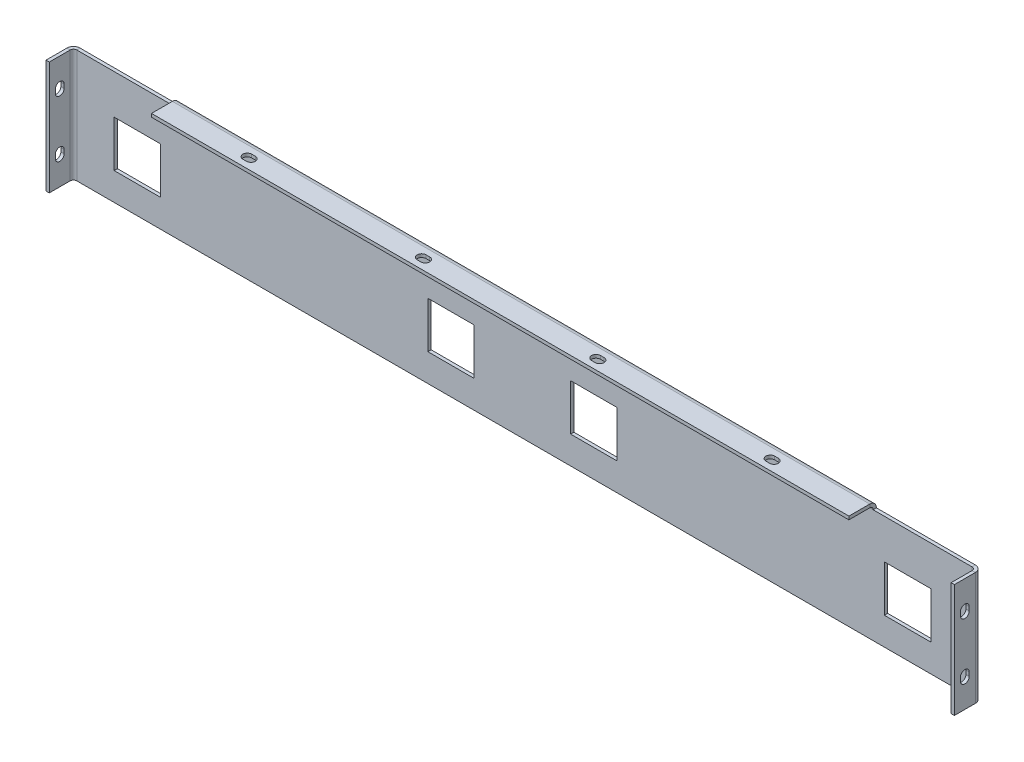
SolidWorks part; units mm, degrees
note: The reader was unsure of these and kept them because the rebuilt part matched: flange length of "Edge-Flange1", "Edge-Flange2".
material "6061-T6 (SS)"
ref_plane "X-Y Datum" through (0, 0, 0) normal (0, 0, 1) x (1, 0, 0)
ref_plane "X-Z Datum" through (0, 0, 0) normal (0, 1, 0) x (1, 0, 0)
ref_plane "Y-Z Datum" through (0, 0, 0) normal (1, 0, 0) x (0, 0, -1)
sketch "Sketch1" plane through (0, 0, 0) normal (0, 0, 1) x (1, 0, 0)
  line L0 (-855.7586, -294.6095) -> (-855.7586, -326.6895)
  line L1 (-886.2514, -267.2257) -> (-256.3416, -267.2257)
  line L2 (-886.2514, -267.2257) -> (-886.2514, -345.8463)
  line L3 (-886.2514, -345.8463) -> (-256.3416, -345.8463)
  line L4 (-256.3416, -267.2257) -> (-256.3416, -345.8463)
  line L5 (-853.2186, -297.1495) -> (-826.2186, -297.1495) construction
  line L6 (-853.2186, -297.1495) -> (-853.2186, -324.1495) construction
  line L7 (-853.2186, -324.1495) -> (-826.2186, -324.1495) construction
  line L8 (-826.2186, -297.1495) -> (-826.2186, -324.1495) construction
  line L9 (-635.6448, -297.1495) -> (-608.6448, -297.1495) construction
  line L10 (-635.6448, -297.1495) -> (-635.6448, -324.1495) construction
  line L11 (-635.6448, -324.1495) -> (-608.6448, -324.1495) construction
  line L12 (-608.6448, -297.1495) -> (-608.6448, -324.1495) construction
  line L13 (-536.6762, -297.1495) -> (-509.4787, -297.1495) construction
  line L14 (-536.6762, -297.1495) -> (-536.6762, -324.1495) construction
  line L15 (-536.6762, -324.1495) -> (-509.4787, -324.1495) construction
  line L16 (-509.4787, -297.1495) -> (-509.4787, -324.1495) construction
  line L17 (-319.1024, -297.1495) -> (-291.7817, -297.1495) construction
  line L18 (-319.1024, -297.1495) -> (-319.1024, -324.1495) construction
  line L19 (-319.1024, -324.1495) -> (-291.7817, -324.1495) construction
  line L20 (-291.7817, -297.1495) -> (-291.7817, -324.1495) construction
  line L21 (-855.7586, -326.6895) -> (-823.6786, -326.6895)
  line L22 (-823.6786, -294.6095) -> (-823.6786, -326.6895)
  line L23 (-855.7586, -294.6095) -> (-823.6786, -294.6095)
  line L24 (-638.1848, -294.6095) -> (-638.1848, -326.6895)
  line L25 (-638.1848, -326.6895) -> (-606.1048, -326.6895)
  line L26 (-606.1048, -294.6095) -> (-606.1048, -326.6895)
  line L27 (-638.1848, -294.6095) -> (-606.1048, -294.6095)
  line L28 (-539.2162, -294.6095) -> (-539.2162, -326.6895)
  line L29 (-539.2162, -326.6895) -> (-506.9387, -326.6895)
  line L30 (-506.9387, -294.6095) -> (-506.9387, -326.6895)
  line L31 (-539.2162, -294.6095) -> (-506.9387, -294.6095)
  line L32 (-321.6424, -294.6095) -> (-321.6424, -326.6895)
  line L33 (-321.6424, -326.6895) -> (-289.2417, -326.6895)
  line L34 (-289.2417, -294.6095) -> (-289.2417, -326.6895)
  line L35 (-321.6424, -294.6095) -> (-289.2417, -294.6095)
  point P41 (-256.3416, -267.2257)
  dimension "D1" = 2.54
  dimension "D2" = 2.54
  dimension "D3" = 2.54
  dimension "D4" = 2.54
base flange "Base-Flange1" sketch "Sketch1" thickness 2.286 reverse thickness direction no parameters "D1"=9.525
edge flange "Edge-Flange1" sketch "Sketch21" flange profiles "Sketch21", "Sketch22" flange angle 90 flange length 19.05 flange position material inside bend radius 2.286 thickness 2.286 relief rectangular parameters "D6"=10, "D8"=1
sketch "Sketch21" plane through (-256.3416, 0, 0) normal (1, 0, 0) x (0, 1, 0)
  line L0 (-345.8463, 0) -> (-267.2257, 0) construction
  line L1 (-345.8463, 0) -> (-267.2257, 0)
  line L2 (-345.8463, 0) -> (-345.8463, 16.764)
  line L3 (-345.8463, 16.764) -> (-267.2257, 16.764)
  line L4 (-267.2257, 16.764) -> (-267.2257, 0)
sketch "Sketch22" plane through (-886.2514, 0, 0) normal (-1, 0, 0) x (0, -1, 0)
  line L0 (267.2257, 0) -> (345.8463, 0) construction
  line L1 (267.2257, 0) -> (345.8463, 0)
  line L2 (267.2257, 0) -> (267.2257, 16.764)
  line L3 (267.2257, 16.764) -> (345.8463, 16.764)
  line L4 (345.8463, 16.764) -> (345.8463, 0)
bend "EdgeBend2" bend radius 2.286 bend angle 90 parameters "D5"=2
bend "EdgeBend3" bend radius 2.286 bend angle 90 parameters "D5"=3
edge flange "Edge-Flange2" sketch "Sketch25" flange angle 90 flange length 19.05 flange position bend outside bend radius 2.286 thickness 2.286 relief rectangular parameters "D6"=10
sketch "Sketch25" plane through (0, -267.2257, 0) normal (0, 1, 0) x (-1, 0, 0)
  line L0 (260.9136, 0) -> (881.6794, 0) construction
  line L1 (329.4936, 0) -> (813.0994, 0)
  line L3 (329.4936, 16.764) -> (813.0994, 16.764)
  line L9 (329.4936, 16.764) -> (329.4936, 0)
  line L11 (813.0994, 16.764) -> (813.0994, 0)
bend "EdgeBend4" bend radius 2.286 bend angle 90 parameters "D5"=4
sketch "Sketch26" plane through (-886.2514, 0, 0) normal (-1, 0, 0) x (0, 0, 1)
  line L0 (9.525, -267.2257) -> (9.525, -306.536) construction
  line L3 (16.764, -267.2257) -> (2.286, -267.2257) construction
  line L4 (9.525, -306.536) -> (9.525, -345.8463) construction
  line L5 (2.286, -345.8463) -> (16.764, -345.8463) construction
  line L6 (9.525, -285.6108) -> (9.525, -288.1508) construction
  line L7 (12.575, -285.6108) -> (12.575, -288.1508)
  line L8 (6.475, -285.6108) -> (6.475, -288.1508)
  line L9 (9.525, -306.536) -> (26.9334, -306.536) construction
  line L10 (9.525, -327.4611) -> (9.525, -324.9211) construction
  line L11 (12.575, -327.4611) -> (12.575, -324.9211)
  line L12 (6.475, -327.4611) -> (6.475, -324.9211)
  arc A1 (12.575, -285.6108) -> (6.475, -285.6108) centre (9.525, -285.6108) ccw
  arc A2 (6.475, -288.1508) -> (12.575, -288.1508) centre (9.525, -288.1508) ccw
  arc A3 (12.575, -327.4611) -> (6.475, -327.4611) centre (9.525, -327.4611) cw
  arc A4 (6.475, -324.9211) -> (12.575, -324.9211) centre (9.525, -324.9211) cw
  point P4 (9.525, -286.8808)
  point P6 (9.525, -306.536)
  point P9 (9.525, -326.1911)
  point P12 (9.525, -286.8808)
  point P20 (9.525, -326.1911)
extrude "Cut-Extrude2" cut sketch "Sketch26" against normal through all normal cut yes
sketch "Sketch27" plane through (0, -264.9397, 0) normal (0, -1, 0) x (1, 0, 0)
  line L0 (-571.2965, 16.764) -> (-571.2965, 2.286) construction
  line L1 (-813.0994, 16.764) -> (-329.4936, 16.764) construction
  line L2 (-329.4936, 2.286) -> (-813.0994, 2.286) construction
  line L3 (-692.198, 9.525) -> (-813.0994, 9.525) construction
  line L4 (-753.9187, 9.525) -> (-751.3787, 9.525) construction
  line L5 (-692.198, 16.764) -> (-692.198, 2.286) construction
  line L6 (-813.0994, 2.286) -> (-813.0994, 16.764) construction
  line L7 (-692.198, 9.525) -> (-571.2965, 9.525) construction
  line L8 (-753.9187, 12.575) -> (-751.3787, 12.575)
  line L9 (-753.9187, 6.475) -> (-751.3787, 6.475)
  line L10 (-630.4773, 9.525) -> (-633.0173, 9.525) construction
  line L11 (-630.4773, 12.575) -> (-633.0173, 12.575)
  line L12 (-630.4773, 6.475) -> (-633.0173, 6.475)
  line L13 (-388.6743, 9.525) -> (-391.2143, 9.525) construction
  line L14 (-388.6743, 12.575) -> (-391.2143, 12.575)
  line L15 (-388.6743, 6.475) -> (-391.2143, 6.475)
  line L16 (-512.1158, 9.525) -> (-509.5758, 9.525) construction
  line L17 (-512.1158, 12.575) -> (-509.5758, 12.575)
  line L18 (-512.1158, 6.475) -> (-509.5758, 6.475)
  arc A0 (-753.9187, 12.575) -> (-753.9187, 6.475) centre (-753.9187, 9.525) ccw
  arc A1 (-751.3787, 6.475) -> (-751.3787, 12.575) centre (-751.3787, 9.525) ccw
  arc A2 (-630.4773, 12.575) -> (-630.4773, 6.475) centre (-630.4773, 9.525) cw
  arc A3 (-633.0173, 6.475) -> (-633.0173, 12.575) centre (-633.0173, 9.525) cw
  arc A4 (-388.6743, 12.575) -> (-388.6743, 6.475) centre (-388.6743, 9.525) cw
  arc A5 (-391.2143, 6.475) -> (-391.2143, 12.575) centre (-391.2143, 9.525) cw
  arc A6 (-512.1158, 12.575) -> (-512.1158, 6.475) centre (-512.1158, 9.525) ccw
  arc A7 (-509.5758, 6.475) -> (-509.5758, 12.575) centre (-509.5758, 9.525) ccw
  point P15 (-752.6487, 9.525)
  point P22 (-631.7473, 9.525)
  point P29 (-389.9443, 9.525)
  point P36 (-510.8458, 9.525)
  dimension "D1" = 120.9015
extrude "Cut-Extrude3" cut sketch "Sketch27" against normal through all normal cut yes
sketch "Bend-Lines1" [suppressed] plane through (0, 0, 0) normal (0, 1, 0) x (1, 0, 0)
sketch "Bounding-Box1" [suppressed] plane through (0, 0, 0) normal (0, 1, 0) x (1, 0, 0)
sheet metal parameters "Sheet-Metal1" thickness 2.286 parameters "D1"=9.525
flat pattern "Flat-Pattern1" [suppressed]
sketch "Bend-Lines2" plane through (0, 0, 0) normal (0, 1, 0) x (1, 0, 0)
sketch3d "Bounding-Box2" [suppressed]
  line L0 (886.2514, -345.8463, 0) -> (259.0696, -345.8463, 0) construction
  line L1 (886.2514, -264.5079, 0) -> (259.0696, -264.5079, 0) construction
  line L2 (886.2514, -345.8463, 0) -> (886.2514, -264.5079, 0) construction
  line L3 (259.0696, -345.8463, 0) -> (259.0696, -264.5079, 0) construction
sheet metal parameters "Sheet-Metal2" thickness 2.286 parameters "D1"=9.525
flat pattern "Flat-Pattern1"
sketch "Bend-Lines2" plane through (0, 0, 0) normal (0, 0, 1) x (1, 0, 0)
  line L0 (-884.3726, -264.5079) -> (-884.3726, -345.8463) construction
  line L1 (-258.2205, -345.8463) -> (-258.2205, -264.5079) construction
  line L3 (-884.3726, -264.5079) -> (-884.3726, -345.8463) construction
  line L4 (-258.2205, -345.8463) -> (-258.2205, -264.5079) construction
  point P4 (-324.9216, -266.3867)
  point P5 (-817.6714, -266.3867)
sketch3d "Bounding-Box2" [suppressed]
  line L0 (-901.5437, -345.8463, 0) -> (-241.0493, -345.8463, 0) construction
  line L1 (-901.5437, -264.5079, 0) -> (-241.0493, -264.5079, 0) construction
  line L2 (-901.5437, -345.8463, 0) -> (-901.5437, -264.5079, 0) construction
  line L3 (-241.0493, -345.8463, 0) -> (-241.0493, -264.5079, 0) construction
bend of the flat pattern "Flatten-<EdgeBend2>1"
bend of the flat pattern "Flatten-<EdgeBend3>1"
sheet metal parameters "Sheet-Metal4" thickness 2.286 parameters "D1"=9.525
flat pattern "Flat-Pattern1"
sketch "Bend-Lines2" plane through (0, 0, 0) normal (0, 0, 1) x (1, 0, 0)
  line L0 (-884.3726, -267.2257) -> (-884.3726, -345.8463) construction
  line L1 (-258.2205, -345.8463) -> (-258.2205, -267.2257) construction
  line L2 (-329.4936, -264.5325) -> (-813.0994, -264.5325) construction
  line L3 (-884.3726, -267.2257) -> (-884.3726, -345.8463) construction
  line L4 (-258.2205, -345.8463) -> (-258.2205, -267.2257) construction
  line L5 (-329.4936, -264.5325) -> (-813.0994, -264.5325) construction
sketch3d "Bounding-Box2" [suppressed]
  line L0 (-901.5437, -345.8463, 0) -> (-241.0493, -345.8463, 0) construction
  line L1 (-901.5437, -247.3614, 0) -> (-241.0493, -247.3614, 0) construction
  line L2 (-901.5437, -345.8463, 0) -> (-901.5437, -247.3614, 0) construction
  line L3 (-241.0493, -345.8463, 0) -> (-241.0493, -247.3614, 0) construction
bend of the flat pattern "Flatten-<EdgeBend2>1"
bend of the flat pattern "Flatten-<EdgeBend3>1"
bend of the flat pattern "Flatten-<EdgeBend4>1"
sheet metal parameters "Sheet-Metal5" thickness 2.286 parameters "D1"=9.525
flat pattern "Flat-Pattern1"
sketch "Bend-Lines2" plane through (0, 0, 0) normal (0, 0, 1) x (1, 0, 0)
  line L0 (-884.3726, -267.2257) -> (-884.3726, -345.8463) construction
  line L1 (-258.2205, -345.8463) -> (-258.2205, -267.2257) construction
  line L2 (-329.4936, -264.5325) -> (-813.0994, -264.5325) construction
  line L3 (-884.3726, -267.2257) -> (-884.3726, -345.8463) construction
  line L4 (-258.2205, -345.8463) -> (-258.2205, -267.2257) construction
  line L5 (-329.4936, -264.5325) -> (-813.0994, -264.5325) construction
sketch3d "Bounding-Box2" [suppressed]
  line L0 (-901.5437, -345.8463, 0) -> (-241.0493, -345.8463, 0) construction
  line L1 (-901.5437, -247.3614, 0) -> (-241.0493, -247.3614, 0) construction
  line L2 (-901.5437, -345.8463, 0) -> (-901.5437, -247.3614, 0) construction
  line L3 (-241.0493, -345.8463, 0) -> (-241.0493, -247.3614, 0) construction
bend of the flat pattern "Flatten-<EdgeBend2>1"
bend of the flat pattern "Flatten-<EdgeBend3>1"
bend of the flat pattern "Flatten-<EdgeBend4>1"
sheet metal parameters "Sheet-Metal6" thickness 2.286 parameters "D1"=9.525
flat pattern "Flat-Pattern1"
sketch "Bend-Lines2" plane through (0, 0, 0) normal (0, 0, 1) x (1, 0, 0)
  line L0 (-884.3726, -267.2257) -> (-884.3726, -345.8463) construction
  line L1 (-258.2205, -345.8463) -> (-258.2205, -267.2257) construction
  line L2 (-329.4936, -264.5325) -> (-813.0994, -264.5325) construction
  line L3 (-884.3726, -267.2257) -> (-884.3726, -345.8463) construction
  line L4 (-258.2205, -345.8463) -> (-258.2205, -267.2257) construction
  line L5 (-329.4936, -264.5325) -> (-813.0994, -264.5325) construction
sketch3d "Bounding-Box2" [suppressed]
  line L0 (-901.5437, -345.8463, 0) -> (-241.0493, -345.8463, 0) construction
  line L1 (-901.5437, -247.3614, 0) -> (-241.0493, -247.3614, 0) construction
  line L2 (-901.5437, -345.8463, 0) -> (-901.5437, -247.3614, 0) construction
  line L3 (-241.0493, -345.8463, 0) -> (-241.0493, -247.3614, 0) construction
bend of the flat pattern "Flatten-<EdgeBend2>1"
bend of the flat pattern "Flatten-<EdgeBend3>1"
bend of the flat pattern "Flatten-<EdgeBend4>1"
